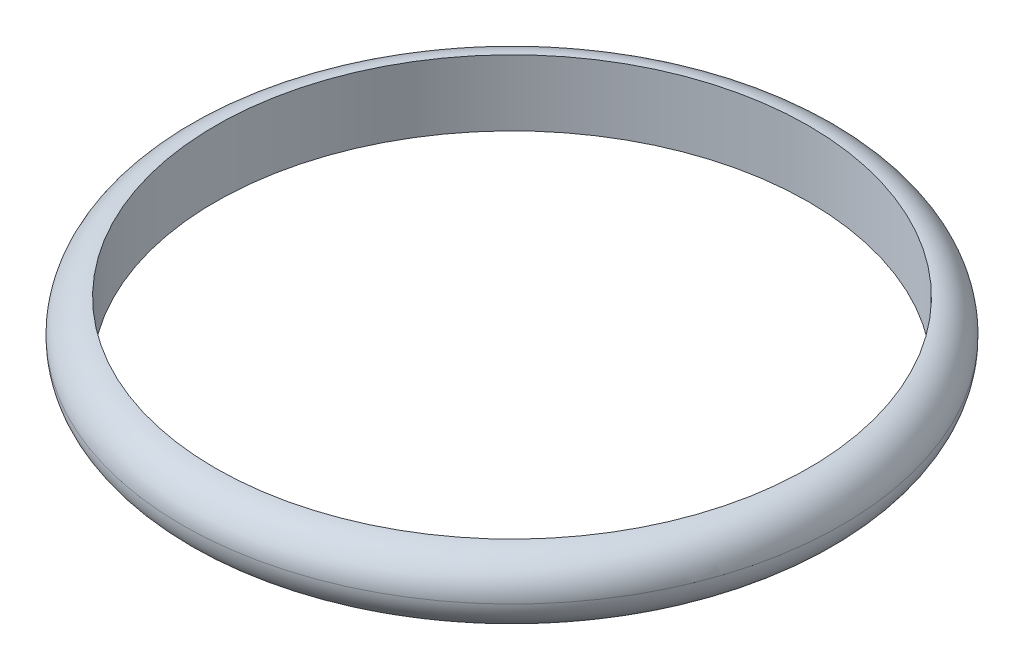
SolidWorks part; units mm, degrees
ref_plane "Face" through (0, 0, 0) normal (0, 0, 1) x (1, 0, 0)
ref_plane "Dessus" through (0, 0, 0) normal (0, 1, 0) x (1, 0, 0)
ref_plane "Droite" through (0, 0, 0) normal (1, 0, 0) x (0, 0, -1)
sketch "Esquisse1" plane through (0, 0, 0) normal (0, 1, 0) x (1, 0, 0)
  circle A0 centre (0, 0) radius 20
  circle A1 centre (0, 0) radius 18
  dimension "D1" = 40
  dimension "D2" = 36
extrude "Extrusion1" add sketch "Esquisse1" along normal blind 4
fillet "Congé1" radius 2 2 edges at (0, 0, 20) (0, 4, 20)
